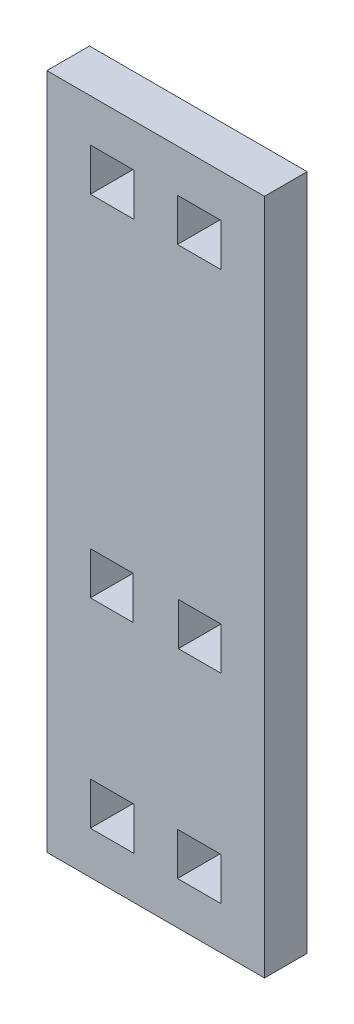
SolidWorks part; units mm, degrees
ref_plane "Front Plane" through (0, 0, 0) normal (0, 0, 1) x (1, 0, 0)
ref_plane "Top Plane" through (0, 0, 0) normal (0, 1, 0) x (1, 0, 0)
ref_plane "Right Plane" through (0, 0, 0) normal (1, 0, 0) x (0, 0, -1)
sketch "Sketch1" plane through (0, 0, 0) normal (0, 0, 1) x (1, 0, 0)
  line L1 (0, 0) -> (25.53, 0)
  line L2 (0, 0) -> (0, 79.4)
  line L3 (0, 79.4) -> (25.53, 79.4)
  line L4 (25.53, 0) -> (25.53, 79.4)
  dimension "D1" = 79.4
  dimension "D2" = 25.53
extrude "Boss-Extrude1" add sketch "Sketch1" along normal blind 5
sketch "Sketch2" plane through (0, 0, 5) normal (0, 0, 1) x (1, 0, 0)
  line L0 (25.53, 39.7) -> (-17.1954, 39.7) construction
  line L1 (2.75, 0) -> (-2.75, 0) construction
  line L2 (20.424, 69.3685) -> (25.53, 69.3685) construction
  line L3 (5.106, 74.4) -> (10.212, 74.4)
  line L4 (5.106, 74.4) -> (5.106, 69.4)
  line L5 (5.106, 69.4) -> (10.212, 69.4)
  line L6 (10.212, 74.4) -> (10.212, 69.4)
  line L7 (15.318, 74.4) -> (20.424, 74.4)
  line L8 (15.318, 74.4) -> (15.318, 69.4)
  line L9 (15.318, 69.4) -> (20.424, 69.4)
  line L10 (20.424, 74.4) -> (20.424, 69.4)
  line L11 (25.53, 0) -> (25.53, 79.4) construction
  line L12 (10.212, 71.2882) -> (15.318, 71.2882) construction
  line L13 (5.106, 70.4299) -> (0, 70.4299) construction
  line L14 (0, -2.75) -> (0, 2.75) construction
  line L15 (25.53, 79.4) -> (0, 79.4) construction
  line L16 (5.106, 33.4) -> (10.106, 33.4)
  line L17 (5.106, 33.4) -> (5.106, 28.4)
  line L18 (5.106, 28.4) -> (10.106, 28.4)
  line L19 (10.106, 33.4) -> (10.106, 28.4)
  line L20 (15.424, 33.4) -> (20.424, 33.4)
  line L21 (15.424, 33.4) -> (15.424, 28.4)
  line L22 (15.424, 28.4) -> (20.424, 28.4)
  line L23 (20.424, 33.4) -> (20.424, 28.4)
  line L24 (20.424, 71.9) -> (25.53, 71.9) construction
  line L44 (20.424, 5) -> (20.424, 10)
  line L45 (15.318, 10) -> (20.424, 10)
  line L46 (15.318, 5) -> (20.424, 5)
  line L47 (10.212, 5) -> (10.212, 10)
  line L48 (5.106, 5) -> (10.212, 5)
  line L49 (5.106, 5) -> (5.106, 10)
  line L50 (5.106, 10) -> (10.212, 10)
  line L51 (15.318, 5) -> (15.318, 10)
  dimension "D1" = 5
  dimension "D2" = 5
  dimension "D3" = 5
  dimension "D4" = 5
  dimension "D5" = 5
  dimension "D6" = 36
extrude "Cut-Extrude1" cut sketch "Sketch2" against normal through all
